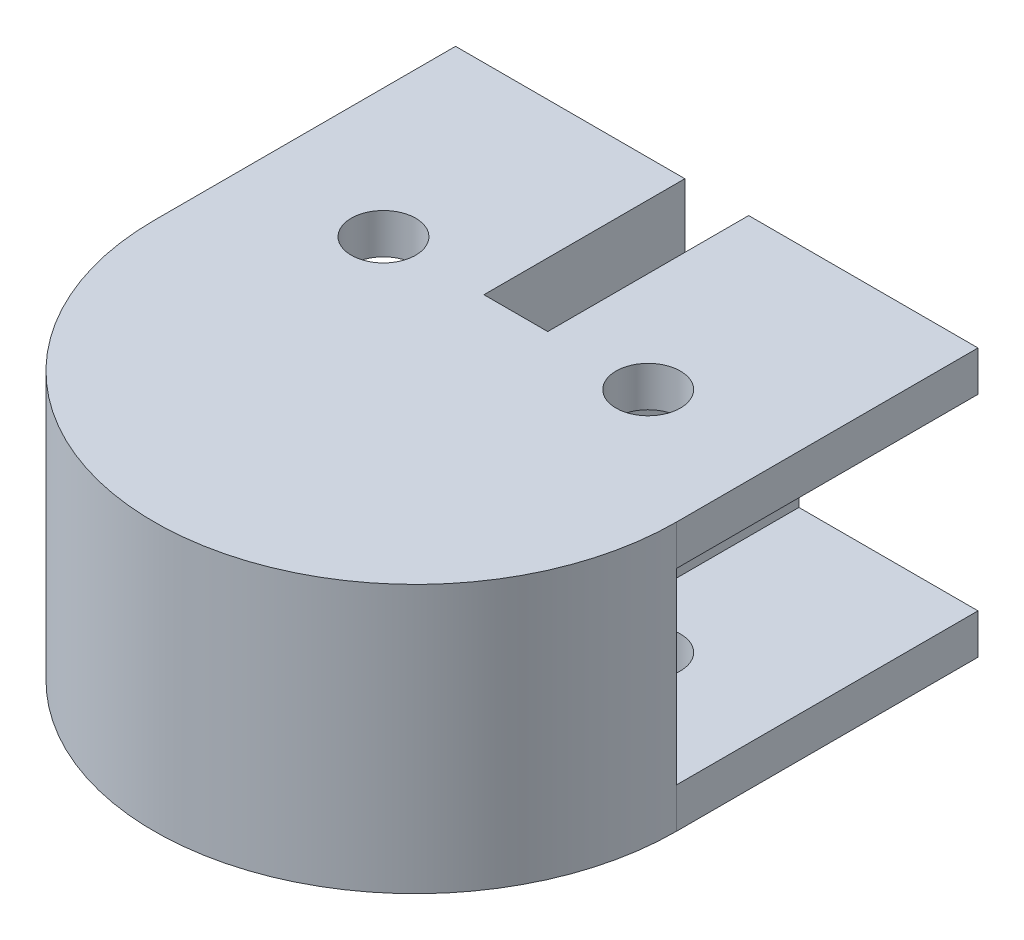
SolidWorks part; units mm, degrees
ref_plane "Front Plane" through (0, 0, 0) normal (0, 0, 1) x (1, 0, 0)
ref_plane "Top Plane" through (0, 0, 0) normal (0, 1, 0) x (1, 0, 0)
ref_plane "Right Plane" through (0, 0, 0) normal (1, 0, 0) x (0, 0, -1)
sketch "Sketch1" plane through (0, 0, 0) normal (0, 1, 0) x (1, 0, 0)
  line L0 (-1.5875, 0) -> (1.5875, 0)
  line L1 (1.5875, 0) -> (1.5875, 10)
  line L2 (1.5875, 10) -> (13, 10)
  line L3 (13, 10) -> (13, -5)
  line L4 (0, 0) -> (0, -18) construction
  line L5 (-13, 10) -> (-13, -5)
  line L6 (-1.5875, 10) -> (-13, 10)
  line L7 (-1.5875, 0) -> (-1.5875, 10)
  arc A0 (-13, -5) -> (13, -5) centre (0, -5) ccw
  circle A1 centre (6.5875, 0) radius 1.6
  circle A2 centre (-6.5875, 0) radius 1.6
  dimension "D5" = 3.2
  dimension "D1" = 1.5875
  dimension "D2" = 11.4125
  dimension "D3" = 15
  dimension "D4" = 10
  dimension "D6" = 5
extrude "Boss-Extrude1" add sketch "Sketch1" along normal blind 2
sketch "Sketch3" plane through (0, 0, 0) normal (0, -1, 0) x (1, 0, 0)
  line L0 (4.0875, -10) -> (1.5875, -10)
  line L1 (13, -10) -> (1.5875, -10) construction
  line L2 (1.5875, -10) -> (1.5875, 0)
  line L3 (1.5875, 0) -> (-1.5875, 0)
  line L4 (-1.5875, 0) -> (-1.5875, -10)
  line L5 (-1.5875, -10) -> (-4.0875, -10)
  line L6 (-1.5875, -10) -> (-13, -10) construction
  line L7 (-4.0875, -10) -> (-4.0875, 5)
  line L8 (-4.0875, 5) -> (-13, 5)
  line L9 (4.0875, -10) -> (4.0875, 5)
  line L10 (4.0875, 5) -> (13, 5)
  arc A0 (13, 5) -> (-13, 5) centre (0, 5) ccw
  dimension "D1" = 2.5
extrude "Boss-Extrude3" add sketch "Sketch3" along normal blind 4.665
ref_plane "Plane2" through (0, -4.665, 0) normal (0, -1, 0) x (-1, 0, 0)
mirror "Mirror11" about plane through (0, -4.665, 0) normal (0, -1, 0) of "Boss-Extrude3"
mirror "Mirror12" about plane through (0, -4.665, 0) normal (0, -1, 0) of "Boss-Extrude1"
